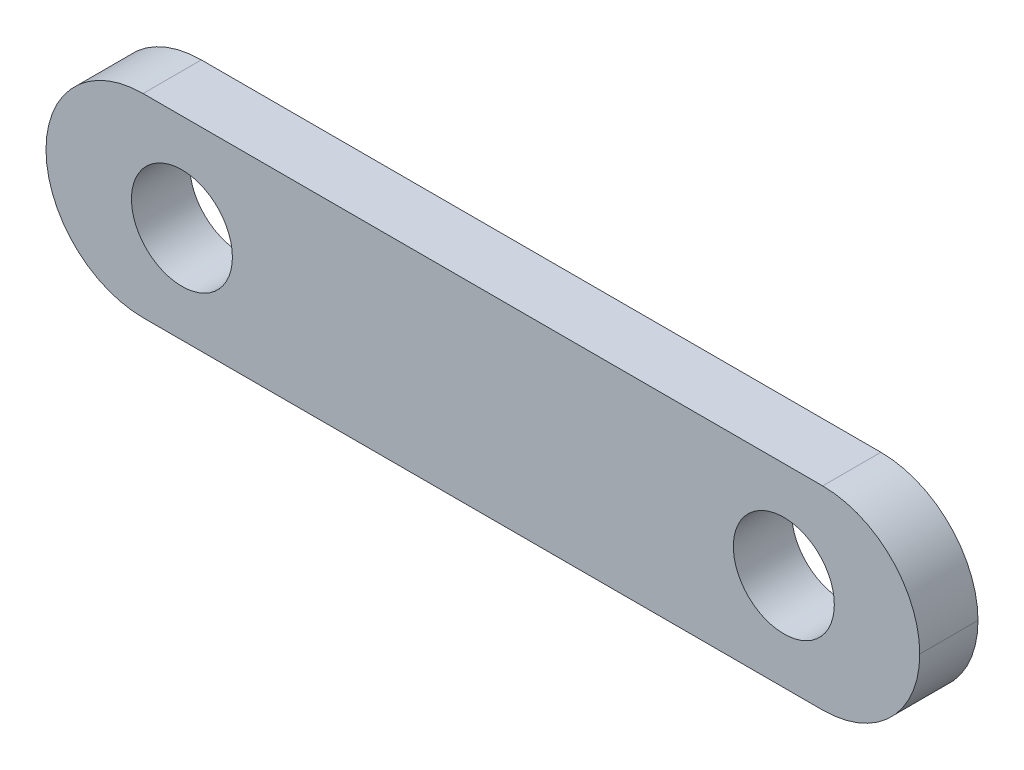
SolidWorks part; units mm, degrees
ref_plane "Plan de face" through (0, 0, 0) normal (0, 0, 1) x (1, 0, 0)
ref_plane "Plan de dessus" through (0, 0, 0) normal (0, 1, 0) x (1, 0, 0)
ref_plane "Plan de droite" through (0, 0, 0) normal (1, 0, 0) x (0, 0, -1)
sketch "Esquisse1" plane through (0, 0, 0) normal (0, 0, 1) x (1, 0, 0)
  line L1 (-47.7033, 11.0231) -> (-2.7033, 11.0231)
  line L2 (-47.7033, 11.0231) -> (-47.7033, 1.0231)
  line L3 (-47.7033, 1.0231) -> (-2.7033, 1.0231)
  line L4 (-2.7033, 11.0231) -> (-2.7033, 1.0231)
  dimension "D1" = 45
  dimension "D2" = 10
extrude "Extrusion1" add sketch "Esquisse1" along normal blind 3
sketch "Esquisse2" plane through (0, 0, 3) normal (0, 0, 1) x (1, 0, 0)
  line L0 (-2.7033, 11.0231) -> (-47.7033, 11.0231) construction
  line L1 (-47.7033, 11.0231) -> (-47.7033, 1.0231) construction
  circle A0 centre (-40.7033, 6.0231) radius 2.6
  circle A1 centre (-9.7033, 6.0231) radius 2.6
  dimension "D1" = 5.2
  dimension "D2" = 5
  dimension "D3" = 7
  dimension "D4" = 31
  dimension "D5" = 5.2
extrude "Enlèv. mat.-Extru.1" cut sketch "Esquisse2" against normal blind 3
fillet "Congé1" radius 5 4 edges at (-47.7033, 1.0231, 1.5) (-2.7033, 1.0231, 1.5) (-2.7033, 11.0231, 1.5) (-47.7033, 11.0231, 1.5)
